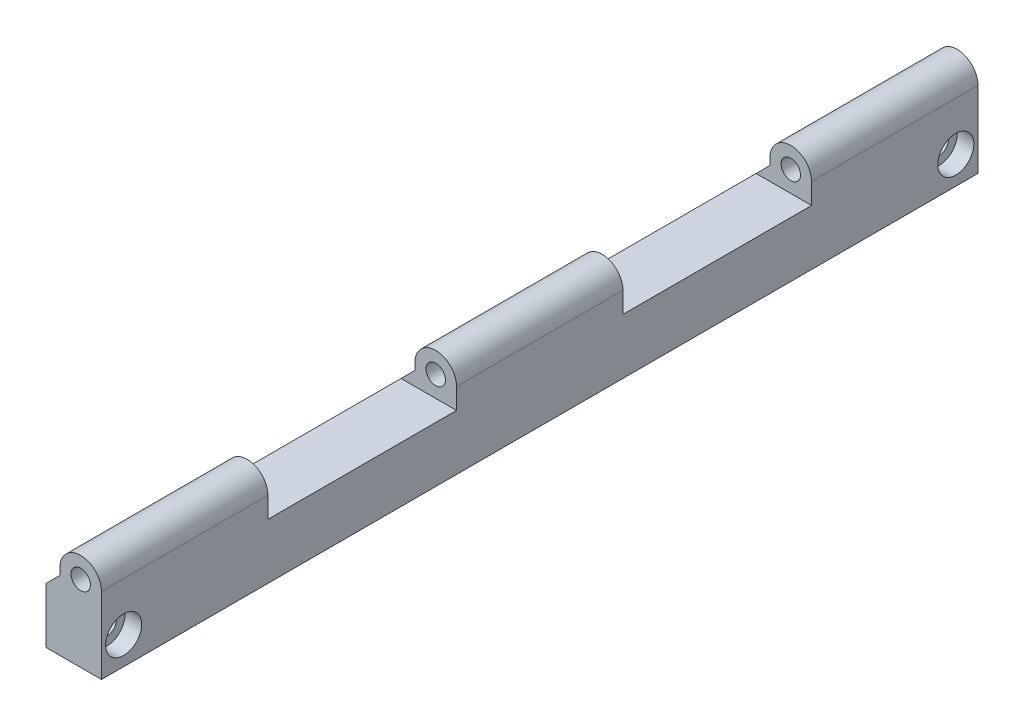
SolidWorks part; units mm, degrees
ref_plane "Plan de face" through (0, 0, 0) normal (0, 0, 1) x (1, 0, 0)
ref_plane "Plan de dessus" through (0, 0, 0) normal (0, 1, 0) x (1, 0, 0)
ref_plane "Plan de droite" through (0, 0, 0) normal (1, 0, 0) x (0, 0, -1)
sketch "Esquisse1" plane through (0, 0, 0) normal (0, 0, 1) x (1, 0, 0)
  line L1 (-5, 5) -> (5, 5)
  line L2 (-5, 5) -> (-5, -5)
  line L3 (-5, -5) -> (5, -5)
  line L4 (5, 5) -> (5, -5)
  line L5 (-5, 5) -> (5, -5) construction
  line L6 (-5, -5) -> (5, 5) construction
  point P0 (0, 0)
  dimension "D1" = 10
extrude "Boss.-Extru.1" add sketch "Esquisse1" along normal mid plane 158
sketch "Esquisse2" plane through (0, 0, -79) normal (0, 0, -1) x (-1, 0, 0)
  line L1 (-5, -5) -> (-5, 5) construction
  line L2 (-5, 5) -> (5, 5) construction
  line L3 (-1.25, 5) -> (-5, 5)
  line L4 (-5, 5) -> (-5, 8.75)
  line L5 (-1.25, 5) -> (2.5, 5)
  line L6 (2.5, 5) -> (2.5, 8.75)
  circle A1 centre (-1.25, 8.75) radius 1.75
  circle A2 centre (-1.25, 8.75) radius 3.75
  line M6 (5, 5) -> (-5, 5)
  dimension "D1" = 3.5
  dimension "D2" = 2
extrude "Boss.-Extru.2" add sketch "Esquisse2" against normal blind 30 contours A2 L4 M6 | A2 A1 | A2 L6 M6 region at (-1.6624, 5.8376, -79) region at (4.1624, 5.8376, -79) region at (3.8267, 6.1733, -79)
pattern_linear "Répétition linéaire1" count 3 spacing 64 along (0, 0, 1) of "Boss.-Extru.2"
hole_wizard "Chambrage pour vis à tête cylindrique à 6 pans creux (ou vis CHC) M31" positions "Esquisse3" profile "Esquisse4" counterbore size "M3" standard "Ansi Metric" end condition through all
sketch "Esquisse3" plane through (5, 0, 0) normal (1, 0, 0) x (0, 0, -1)
  line L0 (-75, 0) -> (75, 0) construction
  point P0 (-75, 0)
  point P2 (75, 0)
  dimension "D1" = 150
sketch "Esquisse4" plane through (5, 0, 75) normal (0, 1, 0) x (0, 0, -1)
  line L0 (0, 0) -> (0, 10)
  line L1 (0, 10) -> (1.7, 10)
  line L3 (1.7, 10) -> (1.7, 3)
  line L4 (1.7, 3) -> (3.25, 3)
  line L5 (3.25, 3) -> (3.25, 0)
  line L7 (3.25, 0) -> (0, 0)
  line L11 (0, -6.35) -> (0, 107.95) construction
  dimension "Diamètre du perçage jusqu'au prochain" = 3.4
  dimension "Profondeur du perçage jusqu'au prochain" = 10
  dimension "Diamètre du chambrage" = 6.5
  dimension "Profondeur du chambrage" = 3
chamfer "Chanfrein1" distance 2.5 angle 45 3 edges at (-2.5, 5, 64) (-2.5, 5, 0) (-2.5, 5, -64)
